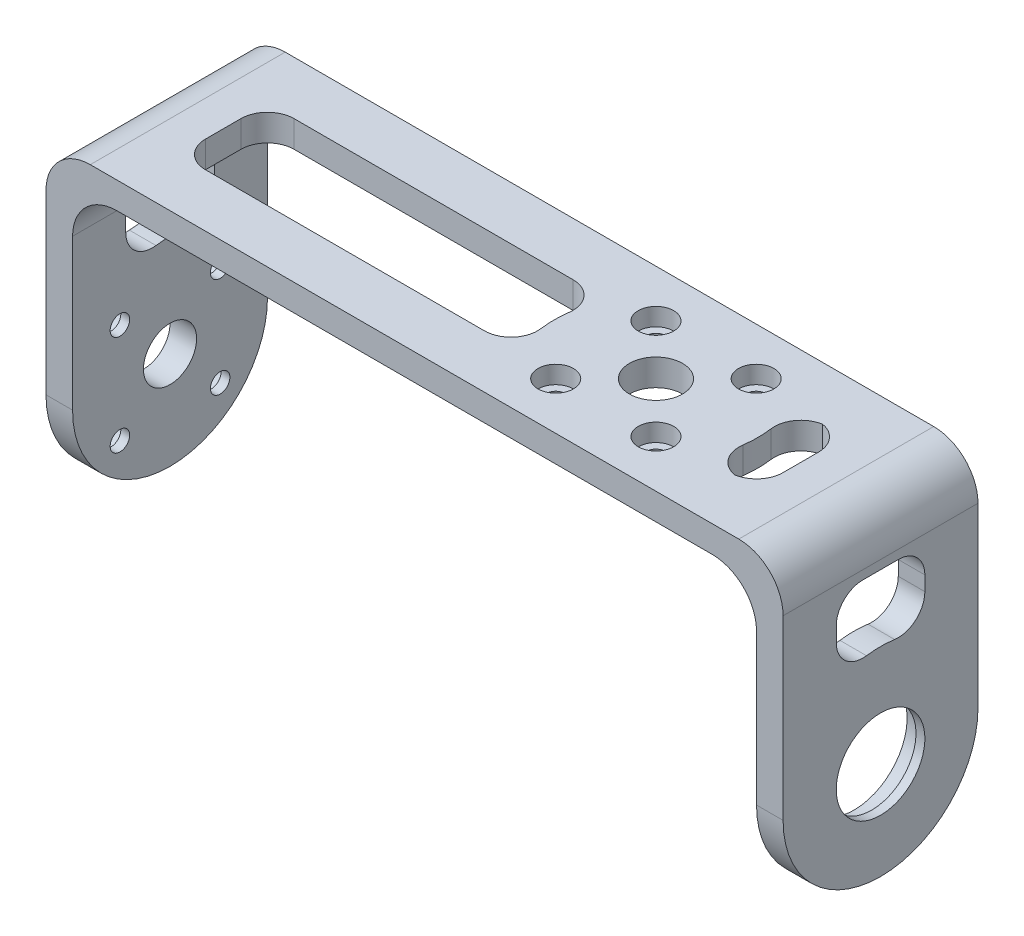
SolidWorks part; units mm, degrees
ref_plane "Front Plane" through (0, 0, 0) normal (0, 0, 1) x (1, 0, 0)
ref_plane "Top Plane" through (0, 0, 0) normal (0, 1, 0) x (1, 0, 0)
ref_plane "Right Plane" through (0, 0, 0) normal (1, 0, 0) x (0, 0, -1)
sketch "Sketch1" plane through (0, 0, 0) normal (0, 1, 0) x (1, 0, 0)
  line L0 (16.25, 0) -> (18.3713, 2.1213) construction
  line L1 (38.6, 11) -> (-38.6, 11)
  line L2 (38.6, 11) -> (38.6, -11)
  line L3 (38.6, -11) -> (-38.6, -11)
  line L4 (-38.6, 11) -> (-38.6, -11)
  line L5 (38.6, 11) -> (-38.6, -11) construction
  line L6 (38.6, -11) -> (-38.6, 11) construction
  line L7 (-38.6, 11) -> (-41.6, 11)
  line L8 (-38.6, 11) -> (-38.6, -11)
  line L9 (-38.6, -11) -> (-41.6, -11)
  line L10 (-41.6, 11) -> (-41.6, -11)
  line L11 (38.6, 11) -> (41.6, 11)
  line L12 (38.6, 11) -> (38.6, -11)
  line L13 (38.6, -11) -> (41.6, -11)
  line L14 (41.6, 11) -> (41.6, -11)
  line L15 (-32.6, 5) -> (-32.6, 11) construction
  line L16 (32.6, 5) -> (26.6062, 5)
  line L17 (32.6, 5) -> (32.6, -5)
  line L18 (32.6, -5) -> (26.6062, -5)
  line L19 (-32.6, 5) -> (-32.6, -5)
  line L20 (32.6, 5) -> (-32.6, -5) construction
  line L21 (32.6, -5) -> (-32.6, 5) construction
  line L22 (-32.6, 5) -> (-38.6, 5) construction
  line L23 (5.8938, 5) -> (-32.6, 5)
  line L24 (5.8938, -5) -> (-32.6, -5)
  circle A0 centre (16.25, 0) radius 3
  arc A1 (5.8938, 5) -> (5.8938, -5) centre (16.25, 0) ccw
  arc A2 (26.6062, -5) -> (26.6062, 5) centre (16.25, 0) ccw
  point P0 (0, 0)
  point P13 (0, 0)
  dimension "D5" = 6
  dimension "D8" = 23
  dimension "D1" = 77.2
  dimension "D2" = 22
  dimension "D3" = 3
  dimension "D4" = 22.35
  dimension "D6" = 45
  dimension "D7" = 6
extrude "Boss-Extrude1" add sketch "Sketch1" against normal blind 3 contours L1 L4 L3 L2 region at (37.7973, 0, 0)
extrude "Boss-Extrude2" add sketch "Sketch1<3>" against normal blind 36 separate body contours L7 L10 L9 L4 | L14 L11 L2 L13 region at (40.1, 0, 0) region at (-40.1, 0, 0)
sketch "Sketch1<3>" plane through (0, 0, 0) normal (0, 1, 0) x (1, 0, 0) same geometry as "Sketch1"
sketch "Sketch2" plane through (-41.6, 0, 0) normal (-1, 0, 0) x (0, 0, 1)
  line L0 (0, -25) -> (5.6569, -19.3431) construction
  line L3 (-11, -36) -> (11, -36) construction
  circle A0 centre (0, -25) radius 3
  circle A1 centre (5.6569, -19.3431) radius 1.1
  dimension "D1" = 6
  dimension "D5" = 2.2
  dimension "D2" = 11
  dimension "D3" = 8
  dimension "D4" = 45
extrude "Cut-Extrude1" cut sketch "Sketch2" against normal up to surface (3 mm away) contours A0 | A1 region at (-41.6, -25, 0) up to face at (-38.6, -18, 0)
sketch "Sketch4" plane through (0, 0, 0) normal (0, 1, 0) x (1, 0, 0)
  line L0 (21.9069, 5.6569) -> (16.25, 0) construction
  line L1 (38.6, 11) -> (-38.6, 11) construction
  circle A0 centre (21.9069, 5.6569) radius 1.1
  dimension "D3" = 2.2
  dimension "D1" = 45
  dimension "D2" = 8
extrude "Cut-Extrude3" cut sketch "Sketch4" against normal up to surface (3 mm away) up to face at (16.25, -3, 3)
pattern_circular "CirPattern2" count 4 over 360 about axis through (16.25, 0, 0) along (0, 1, 0) of "Cut-Extrude3"
sketch "Sketch5" plane through (-41.6, 0, 0) normal (-1, 0, 0) x (0, 0, 1)
  line L0 (-11, -6) -> (-5, -6) construction
  line L2 (-5, -14.6438) -> (-5, -6)
  line L3 (-5, -6) -> (5, -6)
  line L4 (5, -14.6438) -> (5, -6)
  line L5 (-11, -36) -> (-11, 0) construction
  line L6 (-5, -6) -> (-5, 0) construction
  line L7 (55, 0) -> (-55, 0) construction
  line L8 (5, -6) -> (11, -6) construction
  line L9 (11, -36) -> (11, 0) construction
  arc A0 (5, -14.6438) -> (-5, -14.6438) centre (0, -25) ccw
  circle A1 centre (0, -25) radius 3 construction
  dimension "D2" = 23
  dimension "D1" = 6
extrude "Cut-Extrude4" cut sketch "Sketch5" against normal up to surface (83.2 mm away) up to face at (41.6, -18, 0)
sketch "Sketch6" plane through (38.6, 0, 0) normal (-1, 0, 0) x (0, 0, 1)
  circle A0 centre (0, -25) radius 6
  circle A1 centre (0, -25) radius 3 construction
  circle A2 centre (0, -25) radius 5
  dimension "D1" = 12
  dimension "D2" = 10
extrude "Cut-Extrude5" cut sketch "Sketch6" against normal offset from surface (2 mm away) 1 contours A2 | A0 A2 region at (38.6, -25, -5.8303) region at (38.6, -25, 0) up to face at (41.6, -10.036, 0)
extrude "Cut-Extrude6" cut sketch "Sketch6<3>" against normal up to surface (3 mm away) contours A2 region at (38.6, -25, 0) up to face at (41.6, -10.036, 0)
sketch "Sketch6<3>" plane through (38.6, 0, 0) normal (-1, 0, 0) x (0, 0, 1) same geometry as "Sketch6"
combine bodies "Combine1" operation type add bodies to combine 110 108 112
fillet "Fillet2" radius 5 4 edges at (41.6, 0, 0) (-41.6, 0, 0) (38.6, -3, 0) (-38.6, -3, 0)
pattern_circular "CirPattern3" count 4 over 360 about axis through (-30.1147, -25, 0) along (-1, 0, 0) of "Cut-Extrude1" reverse direction yes
fillet "Fillet3" radius 11 4 edges at (40.1, -36, 11) (40.1, -36, -11) (-40.1, -36, -11) (-40.1, -36, 11)
fillet "Fillet4" radius 3 16 edges at (40.1, -14.6438, -5) (40.1, -14.6438, 5) (39.8913, -6, 5) (39.8913, -6, -5) (32.6, -1.5, 5) (26.6062, -1.5, 5) (26.6062, -1.5, -5) (32.6, -1.5, -5) (5.8938, -1.5, 5) (-32.6, -1.5, 5) (-32.6, -1.5, -5) (5.8938, -1.5, -5) (-39.8913, -6, -5) (-39.8913, -6, 5) (-40.1, -14.6438, 5) (-40.1, -14.6438, -5)
sketch "Sketch8" plane through (0, 0, 0) normal (0, 1, 0) x (1, 0, 0)
  circle A0 centre (21.9069, -5.6569) radius 2
  dimension "D1" = 4
extrude "Cut-Extrude7" cut sketch "Sketch8" against normal offset from surface (2 mm away) 1 up to face at (10.5931, -3, -4.5569)
pattern_circular "CirPattern4" count 4 over 360 about axis through (16.25, 0, 0) along (0, 1, 0) of "Cut-Extrude7"
sketch "Sketch9" plane through (-41.6, 0, 0) normal (-1, 0, 0) x (0, 0, 1)
  circle A0 centre (5.6569, -19.3431) radius 2
  dimension "D1" = 4
extrude "Cut-Extrude8" cut sketch "Sketch9" against normal offset from surface (2 mm away) 1 up to face at (-38.6, -19.3431, -4.5569)
pattern_circular "CirPattern5" count 4 over 360 about axis through (-30.1147, -25, 0) along (-1, 0, 0) of "Cut-Extrude8"
